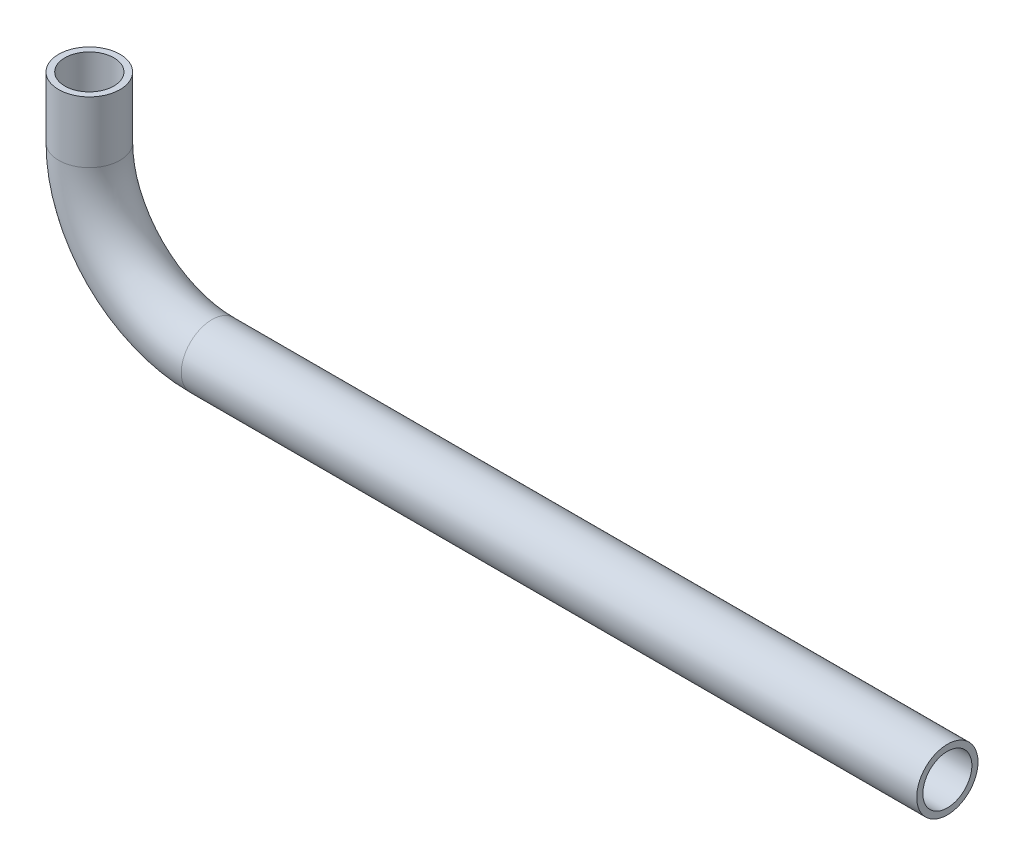
SolidWorks part; units mm, degrees
ref_plane "Front Plane" through (0, 0, 0) normal (0, 0, 1) x (1, 0, 0)
ref_plane "Top Plane" through (0, 0, 0) normal (0, 1, 0) x (1, 0, 0)
ref_plane "Right Plane" through (0, 0, 0) normal (1, 0, 0) x (0, 0, -1)
sketch "Sketch1" plane through (0, 0, 0) normal (0, 0, 1) x (1, 0, 0)
  line L0 (0, 0) -> (120, 0)
  line L1 (-20, 20) -> (-20, 30)
  arc A0 (0, 0) -> (-20, 20) centre (0, 20) cw
  dimension "D2" = 20
  dimension "D1" = 120
  dimension "D3" = 10
sweep "Sweep-Thin1" add path "Sketch1" circular profile diameter 10 parameters "D1"=1, "D3"=10
